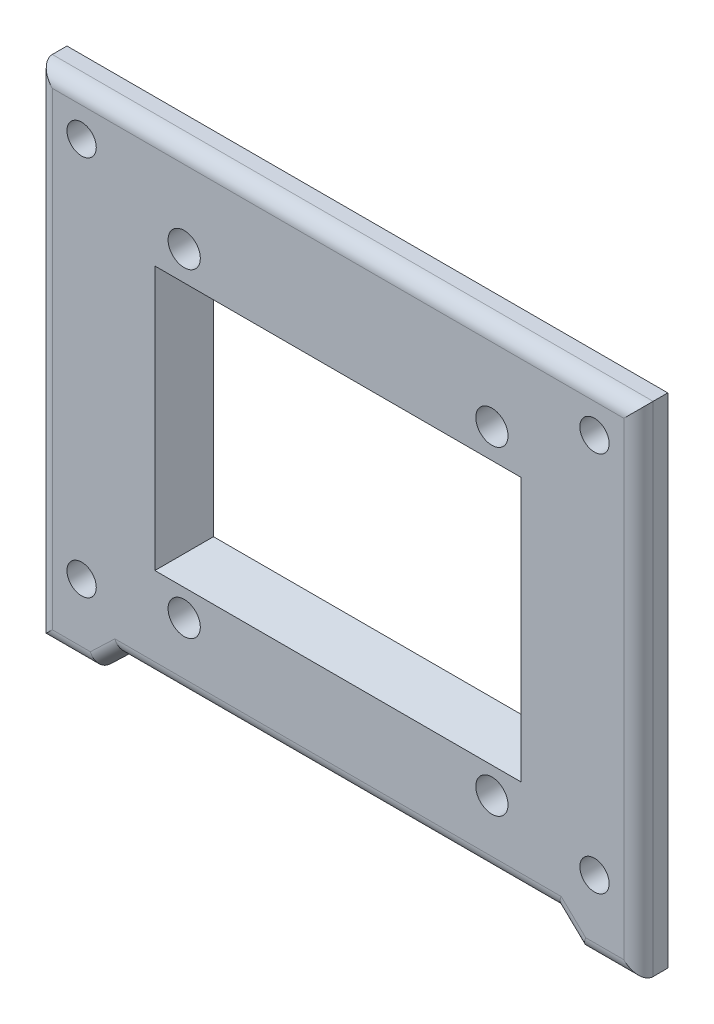
SolidWorks part; units mm, degrees
ref_plane "前视基准面" through (0, 0, 0) normal (0, 0, 1) x (1, 0, 0)
ref_plane "上视基准面" through (0, 0, 0) normal (0, 1, 0) x (1, 0, 0)
ref_plane "右视基准面" through (0, 0, 0) normal (1, 0, 0) x (0, 0, -1)
sketch "草图1" plane through (0, 0, 0) normal (0, 0, 1) x (1, 0, 0)
  line L1 (-11.4284, 14.907) -> (9.5716, 14.907)
  line L2 (-11.4284, 14.907) -> (-11.4284, 0.907)
  line L3 (-11.4284, 0.907) -> (9.5716, 0.907)
  line L4 (9.5716, 14.907) -> (9.5716, 0.907)
  line L5 (-21.4284, 24.907) -> (19.5716, 24.907)
  line L6 (-21.4284, 24.907) -> (-21.4284, -9.093)
  line L7 (-21.4284, -9.093) -> (-17.4284, -9.093)
  line L8 (19.5716, 24.907) -> (19.5716, -9.093)
  line L11 (17.6968, -9.093) -> (19.5716, -9.093)
  line L18 (-0.9284, 24.907) -> (-0.9284, 31.2215) construction
  line L19 (-17.4284, -9.093) -> (-15.7564, -7.493)
  line L20 (-0.9284, 31.2215) -> (-0.9284, -25.8497) construction
  line L21 (-15.7564, -7.493) -> (13.8997, -7.493)
  line L23 (15.5716, -9.093) -> (13.8997, -7.493)
  line L24 (15.5716, -9.093) -> (17.6968, -9.093)
  circle A0 centre (-11.4284, 18.907) radius 1.1
  circle A1 centre (-11.4284, -2.893) radius 1.1
  circle A2 centre (9.5716, 18.907) radius 1.1
  circle A3 centre (9.5716, -2.893) radius 1.1
  point P15 (-0.8749, -7.493)
  point P17 (-0.9284, -7.493)
  point P26 (0, 0)
  dimension "D2" = 2.2
  dimension "D3" = 2.2
  dimension "D4" = 2.2
  dimension "D7" = 2.2
  dimension "D8" = 21.8
  dimension "D9" = 21.8
  dimension "D1" = 14
  dimension "D5" = 10
  dimension "D6" = 10
  dimension "D11" = 0
  dimension "D12" = 4
  dimension "D13" = 4
  dimension "D16" = 21
  dimension "D17" = 10
  dimension "D18" = 10
  dimension "D19" = 34
  dimension "D20" = 41
  dimension "D21" = 4
  dimension "D22" = 1.6
extrude "凸台-拉伸1" add sketch "草图1" along normal blind 2
fillet "圆角2" radius 1 8 edges at (14.7357, -8.293, 2) (-16.5924, -8.293, 2) (-19.4284, -9.093, 2) (-0.9284, -7.493, 2) (17.5716, -9.093, 2) (19.5716, 7.907, 2) (-0.9284, 24.907, 2) (-21.4284, 7.907, 2)
sketch "草图11" plane through (0, 0, 2) normal (0, 0, 1) x (1, 0, 0)
  line L0 (18.5716, 23.907) -> (-20.4284, 23.907) construction
  line L1 (-20.4284, 23.907) -> (-20.4284, -8.093) construction
  line L2 (18.5716, -8.093) -> (18.5716, 23.907) construction
  line L3 (-20.4284, -8.093) -> (-17.8297, -8.093) construction
  line L4 (15.973, -8.093) -> (18.5716, -8.093) construction
  circle A0 centre (-18.4284, 21.907) radius 1
  circle A1 centre (-18.4284, -4.093) radius 1
  circle A2 centre (16.5716, 21.907) radius 1
  circle A3 centre (16.5716, -4.093) radius 1
  dimension "D1" = 2
  dimension "D2" = 2
  dimension "D3" = 2
  dimension "D4" = 2
  dimension "D5" = 2
  dimension "D8" = 2
  dimension "D9" = 2
  dimension "D10" = 2
  dimension "D11" = 4
  dimension "D12" = 4
  dimension "D6" = 2
  dimension "D7" = 2
extrude "切除-拉伸1" cut sketch "草图11" against normal through all
chamfer "倒角1" distance 2 angle 45 4 edges at (-0.9284, 0.907, 2) (9.5716, 7.907, 2) (-11.4284, 7.907, 2) (-0.9284, 14.907, 2)
